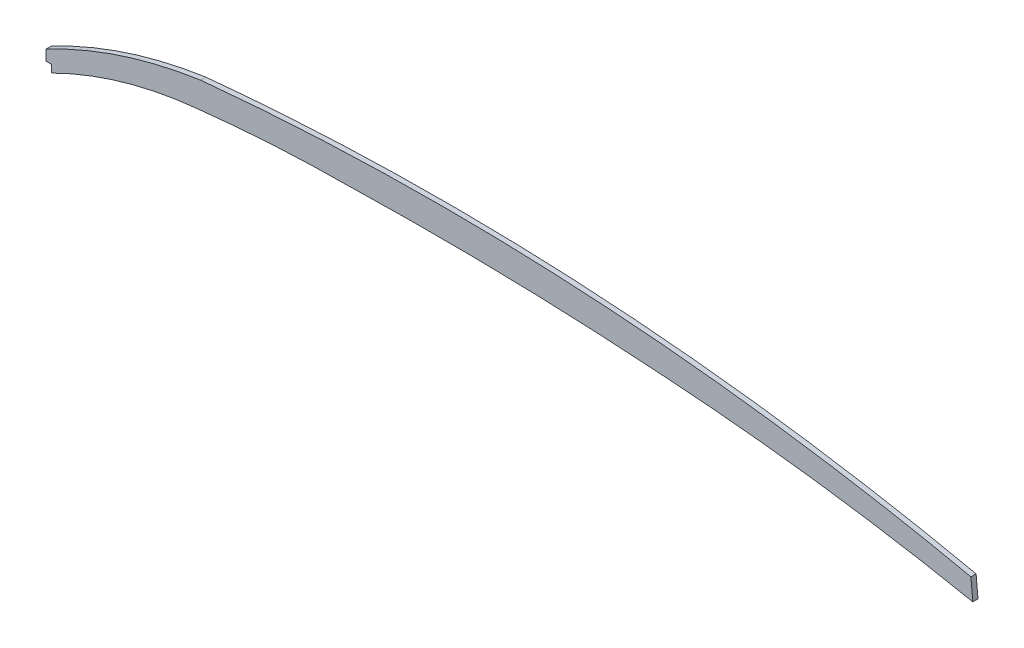
SolidWorks part; units mm, degrees
material "Balsa"
ref_plane "Front Plane" through (0, 0, 0) normal (0, 0, 1) x (1, 0, 0)
ref_plane "Top Plane" through (0, 0, 0) normal (0, 1, 0) x (1, 0, 0)
ref_plane "Right Plane" through (0, 0, 0) normal (1, 0, 0) x (0, 0, -1)
sketch "Sketch1" plane through (0, 0, 0) normal (0, 0, 1) x (1, 0, 0)
  line L0 (0, 85.9422) -> (0, 98.65)
  line L1 (566.0852, 89.3162) -> (564.9321, 101.9672)
  arc A6 (0, 85.9422) -> (92.3925, 113.3643) centre (117.1549, -139.4258) cw
  arc A7 (92.3925, 113.3643) -> (185.8959, 118.7314) centre (190.0181, -770.2591) cw
  arc A8 (0, 98.65) -> (94.4926, 129.4758) centre (136.5172, -159.5853) cw
  arc A9 (185.8959, 118.7314) -> (373.1011, 114.68) centre (236.8429, -1854.3329) cw
  arc A10 (373.1011, 114.68) -> (566.0852, 89.3162) centre (283.2319, -1315.9601) cw
  spline S6 degree 3 poles (2840.1742, -3011.9755) (2207.2857, -1054.6088) (1410.1047, -9.015) (438.4396, 123.9344) (428.6248, 125.18) (408.999, 127.4765) (399.1847, 128.5281) (369.7378, 131.3942) (350.1011, 132.9202) (291.1746, 136.3528) (251.8686, 137.1157) (-696.3591, 118.7732) (-1616.8272, -712.574) (-2553.4552, -2680.697) knots -5.888628 -5.888628 -5.888628 -5.888628 0.25 0.25 0.3125 0.3125 0.375 0.375 0.5 0.5 0.75 0.75 6.527741 6.527741 6.527741 6.527741 only from (564.9321, 101.9672) to (94.4926, 129.4758)
  spline S7 degree 3 poles (564.9321, 101.9672) (526.3055, 110.3588) (487.4057, 117.2346) (438.4396, 123.9344) (428.6248, 125.18) (408.999, 127.4765) (399.1847, 128.5281) (369.7378, 131.3942) (350.1011, 132.9202) (291.1746, 136.3528) (251.8686, 137.1157) (173.2133, 135.5942) (133.864, 133.3099) (94.4926, 129.4758) knots 0 0 0 0 0.25 0.25 0.3125 0.3125 0.375 0.375 0.5 0.5 0.75 0.75 1 1 1 1
  dimension "D4" = 92.3925
  dimension "D2" = 254
  dimension "D8" = 187.2051
  dimension "D9" = 28.7378
  dimension "D1" = 292.1
  dimension "D3" = 889
  dimension "D10" = 1973.7219
  dimension "D11" = 1433.46
  dimension "D5" = 27.4221
  dimension "D6" = 93.5034
  dimension "D7" = 32.7892
  dimension "D12" = 12.7078
extrude "Boss-Extrude1" add sketch "Sketch1" against normal mid plane 3.175 contours L1 S7 A8 L0 A6 A7 A9 A10 region at (279.3924, 119.3664, 0)
sketch "Sketch2" plane through (0, 0, 1.5875) normal (0, 0, 1) x (1, 0, 0)
  line L0 (0, 0) -> (0, 85.9422) construction
  line L3 (0, 85.9422) -> (3.302, 85.9422)
  line L4 (0, 85.9422) -> (0, 92.2922)
  line L5 (0, 92.2922) -> (3.302, 92.2922)
  line L6 (3.302, 85.9422) -> (3.302, 92.2922)
  dimension "D1" = 85.9422
  dimension "D2" = 6.35
  dimension "D3" = 3.302
extrude "Cut-Extrude1" cut sketch "Sketch2" against normal through all
equation "\"slotwidth\"=0.167708"
